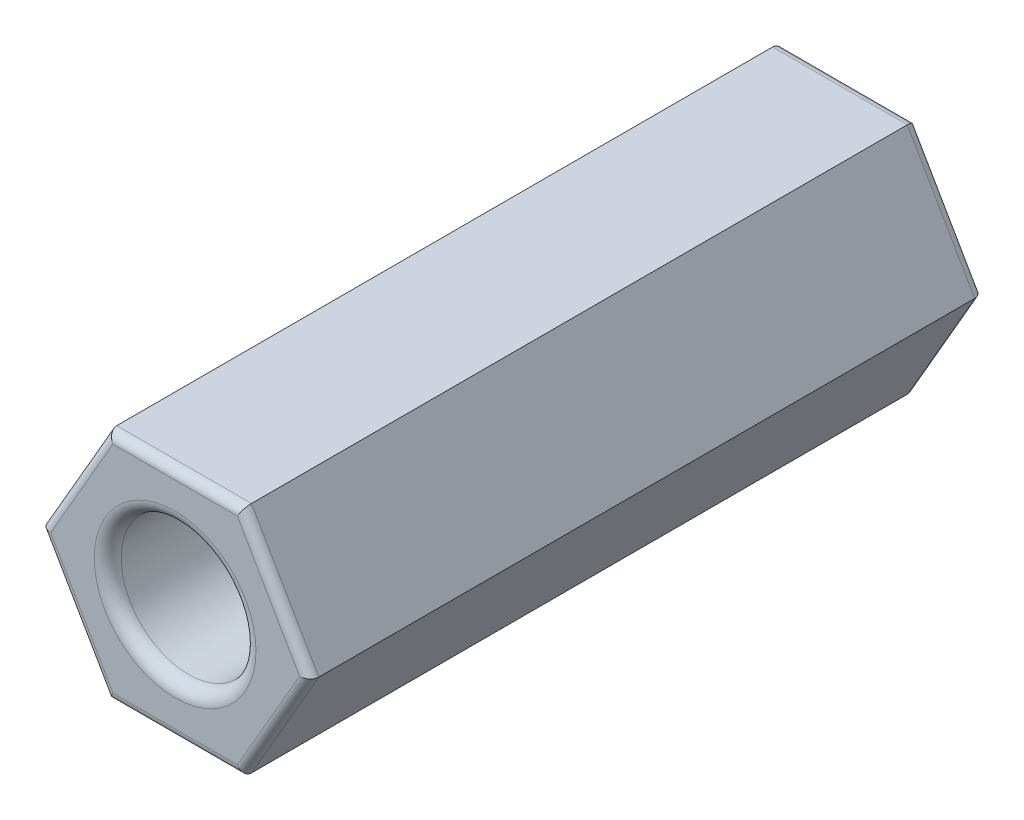
SolidWorks part; units mm, degrees
ref_plane "Front Plane" through (0, 0, 0) normal (0, 0, 1) x (1, 0, 0)
ref_plane "Top Plane" through (0, 0, 0) normal (0, 1, 0) x (1, 0, 0)
ref_plane "Right Plane" through (0, 0, 0) normal (1, 0, 0) x (0, 0, -1)
ref_axis "Axis1" through (0, 0, -81.49) along (0, 0, 1)
sketch "Sketch1" plane through (0, 0, 0) normal (0, 0, 1) x (1, 0, 0)
  line L1 (3, 0) -> (1.5, 2.5981)
  line L2 (1.5, 2.5981) -> (-1.5, 2.5981)
  line L3 (-1.5, 2.5981) -> (-3, 0)
  line L4 (-3, 0) -> (-1.5, -2.5981)
  line L5 (-1.5, -2.5981) -> (1.5, -2.5981)
  line L6 (1.5, -2.5981) -> (3, 0)
  circle A0 centre (0, 0) radius 2.5981 construction
  circle A1 centre (0, 0) radius 1.5
  dimension "D2" = 3
  dimension "D1" = 6
extrude "Boss-Extrude1" add sketch "Sketch1" along normal blind 15
fillet "Fillet1" radius 0.3 2 edges at (1.5, 0, 0) (1.5, 0, 15)
fillet "Fillet2" radius 0.2 12 edges at (-2.25, 1.299, 15) (-2.25, -1.299, 15) (0, -2.5981, 15) (2.25, -1.299, 15) (2.25, 1.299, 15) (0, 2.5981, 15) (2.25, -1.299, 0) (0, -2.5981, 0) (-2.25, -1.299, 0) (-2.25, 1.299, 0) (0, 2.5981, 0) (2.25, 1.299, 0)
sketch "Sketch2" plane through (0, 0, 0) normal (0, 0, 1) x (1, 0, 0)
  circle A0 centre (0, 0) radius 3 construction
